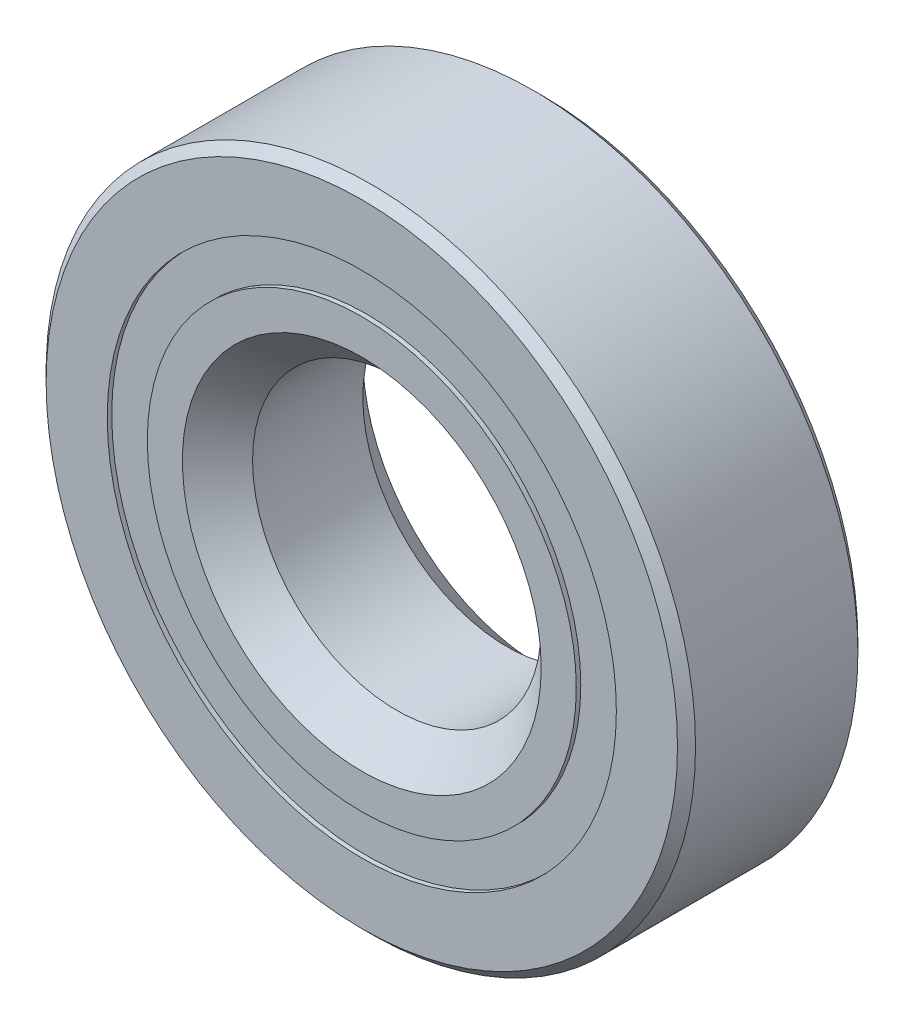
SolidWorks part; units mm, degrees
ref_plane "Front Plane" through (0, 0, 0) normal (0, 0, 1) x (1, 0, 0)
ref_plane "Top Plane" through (0, 0, 0) normal (0, 1, 0) x (1, 0, 0)
ref_plane "Right Plane" through (0, 0, 0) normal (1, 0, 0) x (0, 0, -1)
sketch "Sketch1" plane through (0, 0, 0) normal (1, 0, 0) x (0, 0, -1)
  line L0 (-3.9688, 0) -> (3.9688, 0) construction
  line L1 (0, 14.2875) -> (0, -14.2875) construction
  line L2 (3.5719, 14.2875) -> (-3.5719, 14.2875)
  line L3 (-3.5719, 14.2875) -> (-3.9688, 13.8906)
  line L4 (-3.9688, 13.8906) -> (-3.9688, 11.2007)
  line L5 (-3.9688, 11.2007) -> (-1.7639, 11.2007)
  line L6 (3.9688, 11.2007) -> (1.7639, 11.2007)
  line L7 (3.9688, 13.8906) -> (3.9688, 11.2007)
  line L8 (3.5719, 14.2875) -> (3.9688, 13.8906)
  line L9 (0, 14.2875) -> (0, 10.3187) construction
  line L10 (0, 10.3187) -> (0, 6.35) construction
  arc A0 (-1.7639, 11.2007) -> (1.7639, 11.2007) centre (0, 10.3187) cw
  arc A1 (-1.7639, 11.2007) -> (1.7639, 11.2007) centre (0, 10.3187) ccw construction
  point P14 (0, 6.35)
  point P15 (0, -6.35)
  dimension "Width" = 7.9375
  dimension "OD" = 28.575
  dimension "D1" = 45
  dimension "D2" = 0.3969
  dimension "D3" = 3.5278
  dimension "Shaft Dia" = 12.7
  dimension "D4" = 0.8819
revolve "Revolve1" add sketch "Sketch1" angle 360 about L0
sketch "Sketch2" plane through (0, 0, 0) normal (1, 0, 0) x (0, 0, -1)
  line L0 (-3.9688, 9.4368) -> (-1.7639, 9.4368)
  line L1 (-3.9688, 13.8906) -> (-3.9688, -13.8906) construction
  line L2 (-3.9688, 9.4368) -> (-3.9688, 7.8934)
  line L3 (-3.9688, 7.8934) -> (-2.4253, 6.35)
  line L4 (-2.4253, 6.35) -> (2.4253, 6.35)
  line L5 (0, 14.2875) -> (0, -14.2875) construction
  line L6 (0, 6.35) -> (0, 8.3467) construction
  line L7 (0, 8.3467) -> (0, 6.35) construction
  line L8 (-3.9688, 9.4368) -> (-3.9688, 6.35) construction
  line L9 (-3.9688, 6.35) -> (-2.4253, 6.35) construction
  line L10 (3.9687, 9.4368) -> (1.7639, 9.4368)
  line L11 (3.9687, 9.4368) -> (3.9688, 7.8934)
  line L12 (3.9688, 7.8934) -> (2.4253, 6.35)
  arc A0 (-1.7639, 9.4368) -> (1.7639, 9.4368) centre (0, 10.3187) ccw
  arc A1 (1.7639, 11.2007) -> (-1.7639, 11.2007) centre (0, 10.3187) ccw construction
  circle A2 centre (0, 10.3187) radius 1.9721 construction
  dimension "D1" = 45
revolve "Revolve2" add sketch "Sketch2" angle 360 about L0
sketch "Sketch3" plane through (0, 0, 0) normal (1, 0, 0) x (0, 0, -1)
  line L0 (-1.9721, 10.3187) -> (1.9721, 10.3187)
  line L1 (0, 10.3187) -> (0, 0) construction
  circle A1 centre (0, 10.3187) radius 1.9721 construction
  arc A2 (-1.9721, 10.3187) -> (1.9721, 10.3187) centre (0, 10.3187) cw
  arc A3 (1.7639, 11.2007) -> (-1.7639, 11.2007) centre (0, 10.3187) ccw construction
  dimension "D1" = 3.9442
  dimension "D2" = 10.3187
revolve "Revolve3" add sketch "Sketch3" angle 360 about L0
ref_axis "Axis1" through (0, 0, -3.9688) along (0, 0, 1)
pattern_circular "CirPattern1" count 15 every 24 about axis through (0, 0, -3.9688) along (0, 0, 1) of bodies 104
sketch "Sketch5" plane through (0, 0, 0) normal (1, 0, 0) x (0, 0, -1)
  line L0 (-3.9688, 9.4368) -> (-1.7639, 9.4368) construction
  line L1 (-3.7703, 11.2007) -> (-1.9721, 11.2007)
  line L2 (-3.7703, 11.2007) -> (-3.7703, 9.4368)
  line L3 (-3.7703, 9.4368) -> (-1.9721, 9.4368)
  line L4 (-1.9721, 11.2007) -> (-1.9721, 9.4368)
  line L5 (1.9721, 11.2007) -> (3.7703, 11.2007)
  line L6 (1.9721, 11.2007) -> (1.9721, 9.4368)
  line L7 (1.9721, 9.4368) -> (3.7703, 9.4368)
  line L8 (3.7703, 11.2007) -> (3.7703, 9.4368)
  line L9 (-3.9688, 11.2007) -> (-1.7639, 11.2007) construction
  line L10 (-3.7703, 14.0891) -> (-3.7703, 11.2007) construction
  line L11 (-3.5719, 14.2875) -> (-3.9688, 13.8906) construction
  circle A0 centre (0, 10.3187) radius 1.9721 construction
revolve "Revolve5" add sketch "Sketch5" angle 360 about L0
ref_axis "Center Axis 1" through (0, 0, -6.9885) along (0, 0, 1)
ref_plane "Contact Plane 1" through (0, 0, 3.9688) normal (0, 0, 1) x (1, 0, 0)
ref_plane "Contact Plane 2" through (0, 0, -3.9688) normal (0, 0, -1) x (-1, 0, 0)
equation "\"D2@Sketch1\" = \"Width@Sketch1\"*.05"
equation "\"D3@Sketch1\" = \"Width@Sketch1\"/2.25"
equation "\"D4@Sketch1\" = \"D3@Sketch1\"/4"
equation "\"Balls@CirPattern1\"=\"D2@Sketch3\"*2*pi/\"D1@Sketch3\"-1"
equation "\"D2@CirPattern1\" = 360/\"Balls@CirPattern1\""
